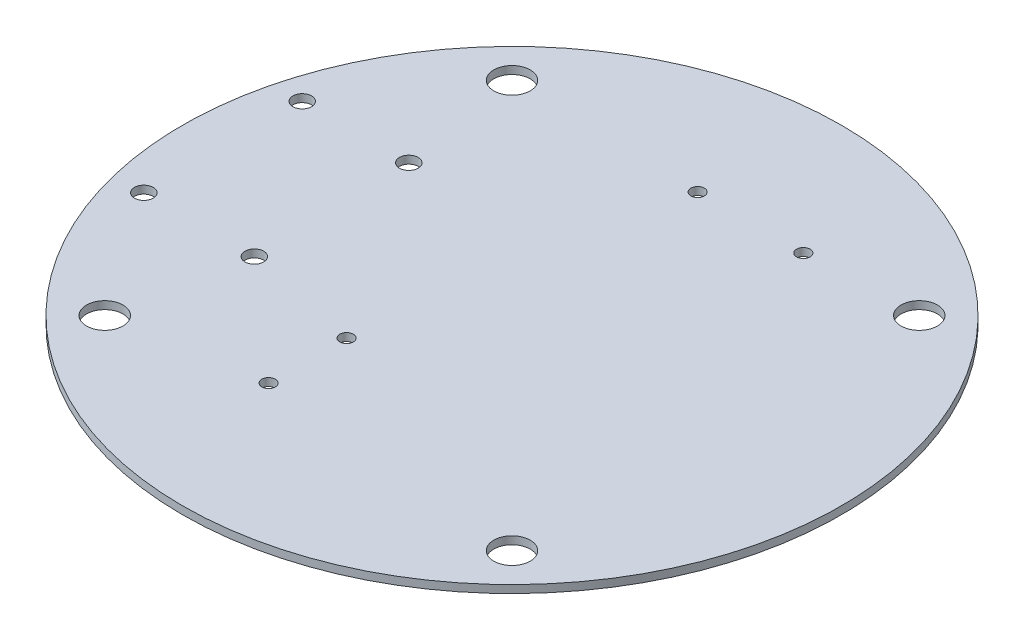
SolidWorks part; units mm, degrees
ref_plane "Front Plane" through (0, 0, 0) normal (0, 0, 1) x (1, 0, 0)
ref_plane "Top Plane" through (0, 0, 0) normal (0, 1, 0) x (1, 0, 0)
ref_plane "Right Plane" through (0, 0, 0) normal (1, 0, 0) x (0, 0, -1)
sketch "Sketch1" plane through (0, 0, 0) normal (0, 1, 0) x (1, 0, 0)
  circle A0 centre (0, 0) radius 63.4
  dimension "PCBdiam" = 126.8
extrude "Boss-Extrude1" add sketch "Sketch1" along normal blind 1.5
hole_wizard "M6 Clearance Hole1" positions "Sketch2" profile "Sketch4" hole size "M6" standard "ANSI Metric" end condition through all
sketch "Sketch2" plane through (0, 1.5, 0) normal (0, 1, 0) x (1, 0, 0)
  line L0 (0, 0) -> (-28.5457, 28.5457) construction
  line L1 (-39.1737, -39.1737) -> (0, 0) construction
  line L3 (0, 0) -> (-73.422, 0) construction
  circle A0 centre (0, 0) radius 63.4 construction
  ellipse E2 centre (-116.4291, -176.9435) end of major axis (-117.7556, -176.0714) minor radius 1.3748
  ellipse E3 centre (-116.4291, -176.9435) end of major axis (-115.1026, -177.8157) minor radius 1.3748
  point P7 (-39.1737, -39.1737)
  dimension "D1" = 0
  dimension "holeRadius" = 55.4
  dimension "D2" = 45
sketch "Sketch4" plane through (-39.1737, 1.5, 39.1737) normal (1, 0, 0) x (0, 0, 1)
  line L0 (0, 0) -> (0, 1.5)
  line L1 (0, 1.5) -> (3.5, 1.5)
  line L2 (3.5, 1.5) -> (3.5, 0)
  line L5 (3.5, 0) -> (0, 0)
  line L11 (0, -6.35) -> (0, 107.95) construction
  dimension "Thru Hole Dia." = 7
  dimension "Thru Hole Depth" = 1.5
pattern_circular "CirPattern1" count 4 over 360 about axis through (0, 1.5, 0) along (0, -1, 0) of "M6 Clearance Hole1"
sketch "Teensy Outline" plane through (0, 1.5, 0) normal (0, 1, 0) x (1, 0, 0)
  line L1 (-29.654, 48.4) -> (-12, 48.4)
  line L2 (-29.654, 48.4) -> (-29.654, -10.02)
  line L3 (-29.654, -10.02) -> (-12, -10.02)
  line L4 (-12, 48.4) -> (-12, -10.02)
  circle A1 centre (0, 0) radius 63.4 construction
  dimension "D1" = 17.654
  dimension "D2" = 58.42
  dimension "D3" = 12
  dimension "D4" = 15
sketch "BMP390 Outline" plane through (0, 1.5, 0) normal (0, 1, 0) x (1, 0, 0)
  line L0 (17.61, 52.4) -> (-5.25, 52.4) construction
  line L2 (20.15, 53.74) -> (-5.25, 53.74)
  line L3 (-5.25, 53.74) -> (-5.25, 35.96)
  line L4 (20.15, 35.96) -> (-5.25, 35.96)
  line L6 (20.15, 53.74) -> (20.15, 35.96)
  line L7 (17.61, 52.4) -> (17.61, 35.96) construction
  line L8 (-29.654, 48.4) -> (-12, 48.4) construction
  line L9 (-12, 48.4) -> (-12, -10.02) construction
  dimension "D1" = 17.78
  dimension "D2" = 25.4
  dimension "D3" = 1.34
  dimension "D4" = 4
  dimension "D5" = 6.75
  dimension "D6" = 5.08
sketch "NEO-6M Outline" plane through (0, 1.5, 0) normal (0, 1, 0) x (1, 0, 0)
  line L0 (-50.84, 17.78) -> (-50.84, 15.24) construction
  line L1 (-58.34, 17.78) -> (-32, 17.78)
  line L2 (-58.34, 17.78) -> (-58.34, -17.78)
  line L3 (-58.34, -17.78) -> (-32, -17.78)
  line L4 (-32, 17.78) -> (-32, -17.78)
  line L5 (-50.84, 15.24) -> (-39.5, 15.24) construction
  line L6 (-39.5, 15.24) -> (-39.5, 17.78) construction
  point P4 (-32, 0)
  point P9 (-45.17, 15.24)
  point P11 (-45.17, 17.78)
  dimension "D1" = 26.34
  dimension "D2" = 35.56
  dimension "D3" = 32
  dimension "D4" = 7.5
  dimension "D5" = 2.54
sketch "Xbee outline" plane through (0, 1.5, 0) normal (0, 1, 0) x (1, 0, 0)
  line L0 (9, 6.5) -> (26, 6.5) construction
  line L1 (26, 1.875) -> (26, 11.125)
  line L2 (26, 11.125) -> (19.5, 18.75)
  line L3 (19.5, 18.75) -> (-7, 18.75)
  line L4 (-7, 18.75) -> (-7, -5.75)
  line L5 (19.5, -5.75) -> (-7, -5.75)
  line L6 (26, 1.875) -> (19.5, -5.75)
  line L7 (0, 0) -> (72.9219, 0) construction
  line L9 (-12, 48.4) -> (-12, -10.02) construction
  line L10 (61, 12) -> (26, 12) construction
  line L11 (61, 12) -> (61, 1) construction
  line L12 (61, 1) -> (26, 1) construction
  line L13 (26, 12) -> (26, 1) construction
  point P7 (-7, 6.5)
  point P11 (26, 6.5)
  dimension "D1" = 24.5
  dimension "D2" = 33
  dimension "D3" = 26.5
  dimension "D4" = 9.25
  dimension "D5" = 16
  dimension "D6" = 35
  dimension "D7" = 11
  dimension "D8" = 6.5
  dimension "D9" = 5
sketch "Accel, gyro outline" plane through (0, 1.5, 0) normal (0, 1, 0) x (1, 0, 0)
  line L0 (47.32, 31.44) -> (27, 31.44) construction
  line L1 (52.4, 32.78) -> (27, 32.78)
  line L2 (27, 32.78) -> (27, 15)
  line L3 (52.4, 15) -> (27, 15)
  line L4 (52.4, 32.78) -> (52.4, 15)
  line L5 (47.32, 31.44) -> (47.32, 16.34) construction
  line L6 (27, 23.89) -> (52.4, 23.89) construction
  line L7 (47.32, 16.34) -> (27, 16.34) construction
  dimension "D1" = 17.78
  dimension "D2" = 25.4
  dimension "D3" = 1.34
  dimension "D4" = 5.08
  dimension "D5" = 15
  dimension "D6" = 27
sketch "Sketch17" plane through (0, 1.5, 0) normal (0, 1, 0) x (1, 0, 0)
  line L0 (-29.654, -23.1737) -> (-36.154, -23.1737) construction
  line L1 (-29.654, -17.1737) -> (-9.654, -17.1737)
  line L2 (-29.654, -17.1737) -> (-29.654, -37.1737)
  line L3 (-29.654, -37.1737) -> (-9.654, -37.1737)
  line L4 (-9.654, -17.1737) -> (-9.654, -37.1737)
  line L5 (-36.154, -23.1737) -> (-36.154, -31.1737) construction
  line L6 (-36.154, -31.1737) -> (-29.654, -31.1737) construction
  line L7 (-29.654, 48.4) -> (-29.654, -10.02) construction
  circle A0 centre (-39.1737, -39.1737) radius 3.5 construction
  point P8 (-36.154, -27.1737)
  point P9 (-29.654, -27.1737)
  dimension "D1" = 20
  dimension "D2" = 20
  dimension "D3" = 6.5
  dimension "D4" = 8
  dimension "D5" = 0
  dimension "D6" = 2
hole_wizard "M2 Clearance Hole1" positions "Sketch20" profile "Sketch19" hole size "M2" standard "ANSI Metric" end condition through all
sketch "Sketch20" plane through (0, 1.5, 0) normal (0, 1, 0) x (1, 0, 0)
  circle A0 centre (-2.71, 38.43) radius 1.2493 construction
  circle A1 centre (17.61, 38.43) radius 1.2493 construction
  circle A2 centre (-12.154, -19.6737) radius 1.25 construction
  circle A3 centre (-12.154, -19.6737) radius 1.25 construction
  circle A4 centre (-12.154, -34.6737) radius 1.25 construction
  circle A5 centre (-12.154, -34.6737) radius 1.25 construction
  point P1 (-2.71, 38.43)
  point P7 (17.61, 38.43)
  point P13 (-12.154, -19.6737)
  point P16 (-12.154, -34.6737)
sketch "Sketch19" plane through (-2.71, 1.5, -38.43) normal (1, 0, 0) x (0, 0, 1)
  line L0 (0, 0) -> (0, 1.5)
  line L1 (0, 1.5) -> (1.3, 1.5)
  line L2 (1.3, 1.5) -> (1.3, 0)
  line L5 (1.3, 0) -> (0, 0)
  line L11 (0, -6.35) -> (0, 107.95) construction
  dimension "Thru Hole Dia." = 2.6
  dimension "Thru Hole Depth" = 1.5
hole_wizard "M3 Clearance Hole2" positions "Sketch21" profile "Sketch22" hole size "M3" standard "ANSI Metric" end condition through all
sketch "Sketch21" plane through (0, 1.5, 0) normal (0, 1, 0) x (1, 0, 0)
  point P0 (-55.8645, 15.5117)
  point P3 (-55.8645, -14.9683)
  point P6 (-34.6045, -14.9683)
  point P9 (-35.3665, 15.5117)
sketch "Sketch22" plane through (-55.8645, 1.5, -15.5117) normal (1, 0, 0) x (0, 0, 1)
  line L0 (0, 0) -> (0, 1.5)
  line L1 (0, 1.5) -> (1.8, 1.5)
  line L2 (1.8, 1.5) -> (1.8, 0)
  line L5 (1.8, 0) -> (0, 0)
  line L11 (0, -6.35) -> (0, 107.95) construction
  dimension "Thru Hole Dia." = 3.6
  dimension "Thru Hole Depth" = 1.5
